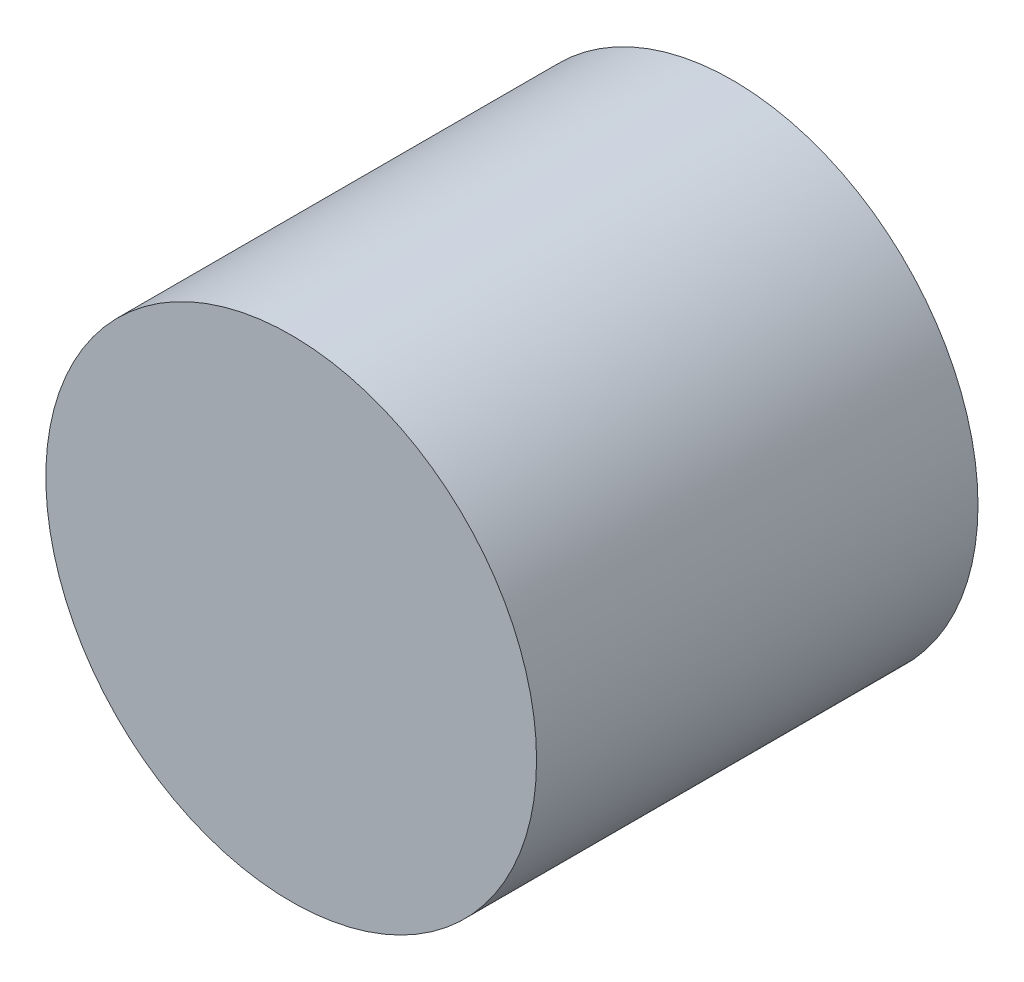
SolidWorks part; units mm, degrees
ref_plane "Front Plane" through (0, 0, 0) normal (0, 0, 1) x (1, 0, 0)
ref_plane "Top Plane" through (0, 0, 0) normal (0, 1, 0) x (1, 0, 0)
ref_plane "Right Plane" through (0, 0, 0) normal (1, 0, 0) x (0, 0, -1)
sketch "Sketch1" plane through (0, 0, 0) normal (0, 0, 1) x (1, 0, 0)
  circle A0 centre (0, 0) radius 38.075
  dimension "D1" = 76.15
extrude "Boss-Extrude1" add sketch "Sketch1" along normal blind 68.5
sketch "Sketch2" plane through (0, 0, 0) normal (0, 0, -1) x (-1, 0, 0)
  circle A0 centre (0, 0) radius 11.5
  dimension "D1" = 23
extrude "Boss-Extrude2" add sketch "Sketch2" along normal blind 6
chamfer "Chamfer1" distance 2 angle 45 1 edges at (-11.5, 0, -6)
sketch "Sketch3" plane through (0, 0, 0) normal (0, 0, -1) x (-1, 0, 0)
  circle A0 centre (0, 0) radius 21.075
  circle A1 centre (0, 0) radius 38.075 construction
  dimension "D1" = 17
extrude "Cut-Extrude1" cut sketch "Sketch3" against normal blind 3
